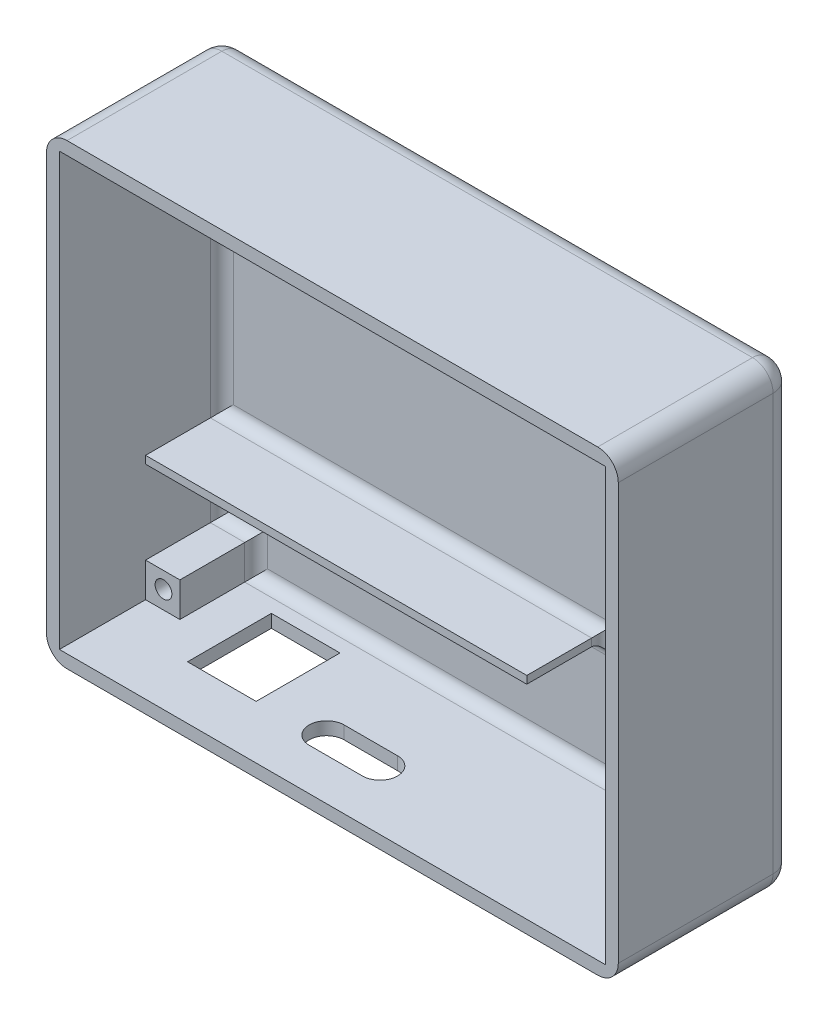
SolidWorks part; units mm, degrees
ref_plane "Front Plane" through (0, 0, 0) normal (0, 0, 1) x (1, 0, 0)
ref_plane "Top Plane" through (0, 0, 0) normal (0, 1, 0) x (1, 0, 0)
ref_plane "Right Plane" through (0, 0, 0) normal (1, 0, 0) x (0, 0, -1)
sketch "Sketch2" plane through (0, 0, 0) normal (0, 0, 1) x (1, 0, 0)
  line L1 (0, 0) -> (75, 0)
  line L2 (0, 0) -> (0, 60)
  line L3 (0, 60) -> (75, 60)
  line L4 (75, 0) -> (75, 60)
  dimension "D1" = 75
  dimension "D2" = 60
extrude "Body creation" add sketch "Sketch2" along normal blind 23
shell "Thikness of walls" thickness 1.7 removed face at (37.5, 30, 23)
ref_plane "Plane1" through (0, 30, 0) normal (0, -1, 0) x (-1, 0, 0)
sketch "Sketch6" plane through (0, 0, 1.7) normal (0, 0, 1) x (1, 0, 0)
  line L1 (1.7, 58.3) -> (6.2, 58.3)
  line L2 (1.7, 58.3) -> (1.7, 53.8)
  line L3 (1.7, 53.8) -> (6.2, 53.8)
  line L4 (6.2, 58.3) -> (6.2, 53.8)
  line L5 (73.3, 58.3) -> (68.8, 58.3)
  line L6 (73.3, 58.3) -> (73.3, 53.8)
  line L7 (73.3, 53.8) -> (68.8, 53.8)
  line L8 (68.8, 58.3) -> (68.8, 53.8)
  dimension "D1" = 4.5
extrude "Corner rect." add sketch "Sketch6" along normal blind 10
sketch "Sketch8" plane through (0, 0, 23) normal (0, 0, 1) x (1, 0, 0)
  line L0 (4.05, 55.95) -> (4.05, 53.8) construction
  line L1 (1.7, 53.8) -> (6.2, 53.8) construction
  line L2 (6.2, 55.95) -> (4.05, 55.95) construction
  line L3 (6.2, 53.8) -> (6.2, 58.3) construction
  line L4 (68.8, 55.95) -> (70.95, 55.95) construction
  line L7 (70.95, 55.95) -> (70.95, 53.8) construction
  line L9 (68.8, 58.3) -> (68.8, 53.8) construction
  line L10 (68.8, 53.8) -> (73.3, 53.8) construction
  circle A0 centre (4.05, 55.95) radius 1.1
  circle A1 centre (70.95, 55.95) radius 1.1
  dimension "D1" = 2.2
  dimension "D2" = 2.15
  dimension "D3" = 2.15
extrude "Screw hole" cut sketch "Sketch8" against normal up to surface (23 mm away) up to face at (37.5, 30, 0)
sketch "Sketch10" plane through (0, 0, 0) normal (0, 0, -1) x (-1, 0, 0)
  circle A0 centre (-70.95, 55.95) radius 1.85
  circle A1 centre (-4.05, 55.95) radius 1.85
  dimension "D1" = 3.7
extrude "Screw head" cut sketch "Sketch10" against normal blind 4
mirror "Mirror to other side" about plane through (0, 30, 0) normal (0, -1, 0) of "Screw head", "Corner rect.", "Screw hole"
sketch "Sketch5" plane through (0, 0, 0) normal (0, -1, 0) x (1, 0, 0)
  line L0 (0, 0) -> (75, 0) construction
  line L1 (20.5, 16) -> (11.5, 16)
  line L2 (20.5, 16) -> (20.5, 5)
  line L3 (20.5, 5) -> (11.5, 5)
  line L4 (11.5, 16) -> (11.5, 5)
  line L5 (0, 23) -> (0, 0) construction
  line L6 (28.95, 15.2) -> (35.95, 15.2) construction
  line L7 (16, 16) -> (16, 5) construction
  line L9 (28.95, 17.5) -> (35.95, 17.5)
  line L10 (28.95, 12.9) -> (35.95, 12.9)
  arc A0 (28.95, 17.5) -> (28.95, 12.9) centre (28.95, 15.2) ccw
  arc A1 (35.95, 12.9) -> (35.95, 17.5) centre (35.95, 15.2) ccw
  point P10 (32.45, 15.2)
  dimension "D6" = 2.3
  dimension "D1" = 11
  dimension "D2" = 9
  dimension "D3" = 16
  dimension "D4" = 16
  dimension "D5" = 7
  dimension "D7" = 11.95
  dimension "D8" = 1.5
extrude "Ports cut out" cut sketch "Sketch5" against normal up to surface (1.7 mm away) up to face at (37.5, 1.7, 12.025)
sketch "Sketch11" plane through (0, 0, 1.7) normal (0, 0, 1) x (1, 0, 0)
  line L0 (1.7, 53.8) -> (1.7, 6.2) construction
  line L1 (6.2, 53.8) -> (51.7, 53.8)
  line L3 (1.7, 18.1) -> (51.7, 18.1)
  line L5 (6.2, 54.8) -> (51.7, 54.8)
  line L6 (1.7, 17.1) -> (51.7, 17.1)
  line L7 (51.7, 18.1) -> (51.7, 17.1)
  line L8 (51.7, 54.8) -> (51.7, 53.8)
  line L9 (6.2, 54.8) -> (6.2, 53.8)
  line L10 (1.7, 18.1) -> (1.7, 17.1)
  line L11 (1.7, 58.3) -> (1.7, 1.7) construction
  line L12 (68.8, 58.3) -> (66.95, 58.3)
  line L13 (68.8, 58.3) -> (68.8, 35.8)
  line L14 (68.8, 35.8) -> (66.95, 35.8)
  line L15 (66.95, 58.3) -> (66.95, 35.8)
  line L16 (68.8, 58.3) -> (68.8, 53.8) construction
  line L18 (68.8, 58.3) -> (6.2, 58.3) construction
  dimension "D1" = 35.7
  dimension "D2" = 50
  dimension "D5" = 65.25
  dimension "D6" = 22.5
  dimension "D3" = 1
  dimension "D4" = 1
extrude "Battery Placement" add sketch "Sketch11" along normal blind 10
fillet "Fillet1" radius 1.5 20 edges at (1.7, 11.65, 1.7) (6.2, 56.55, 1.7) (28.95, 54.8, 1.7) (26.7, 17.1, 1.7) (1.7, 35.95, 1.7) (26.7, 53.8, 1.7) (51.7, 54.3, 1.7) (36.575, 58.3, 1.7) (71.05, 53.8, 1.7) (73.3, 30, 1.7) (71.05, 6.2, 1.7) (68.8, 3.95, 1.7) (37.5, 1.7, 1.7) (6.2, 3.95, 1.7) (3.95, 6.2, 1.7) (51.7, 17.6, 1.7) (26.7, 18.1, 1.7) (66.95, 47.05, 1.7) (67.875, 35.8, 1.7) (68.8, 44.8, 1.7)
fillet "Fillet2" radius 2.7 8 edges at (0, 60, 11.5) (75, 60, 11.5) (75, 0, 11.5) (0, 0, 11.5) (37.5, 60, 0) (75, 30, 0) (37.5, 0, 0) (0, 30, 0)
sketch "Sketch13" plane through (0, 0, 0) normal (0, 0, -1) x (-1, 0, 0)
  line L0 (-37.5, 50) -> (-37.5, 57.3) construction
  line L1 (-62.5, 50) -> (-12.5, 50)
  line L2 (-62.5, 50) -> (-62.5, 10)
  line L3 (-62.5, 10) -> (-12.5, 10)
  line L4 (-12.5, 50) -> (-12.5, 10)
  line L5 (-5.3149, 57.3) -> (-69.6851, 57.3) construction
  line L6 (-62.5, 30) -> (-72.3, 30) construction
  line L7 (-72.3, 54.6851) -> (-72.3, 5.3149) construction
  dimension "D1" = 50
  dimension "D2" = 40
extrude "Cut-Extrude1" cut sketch "Sketch13" against normal blind 1
